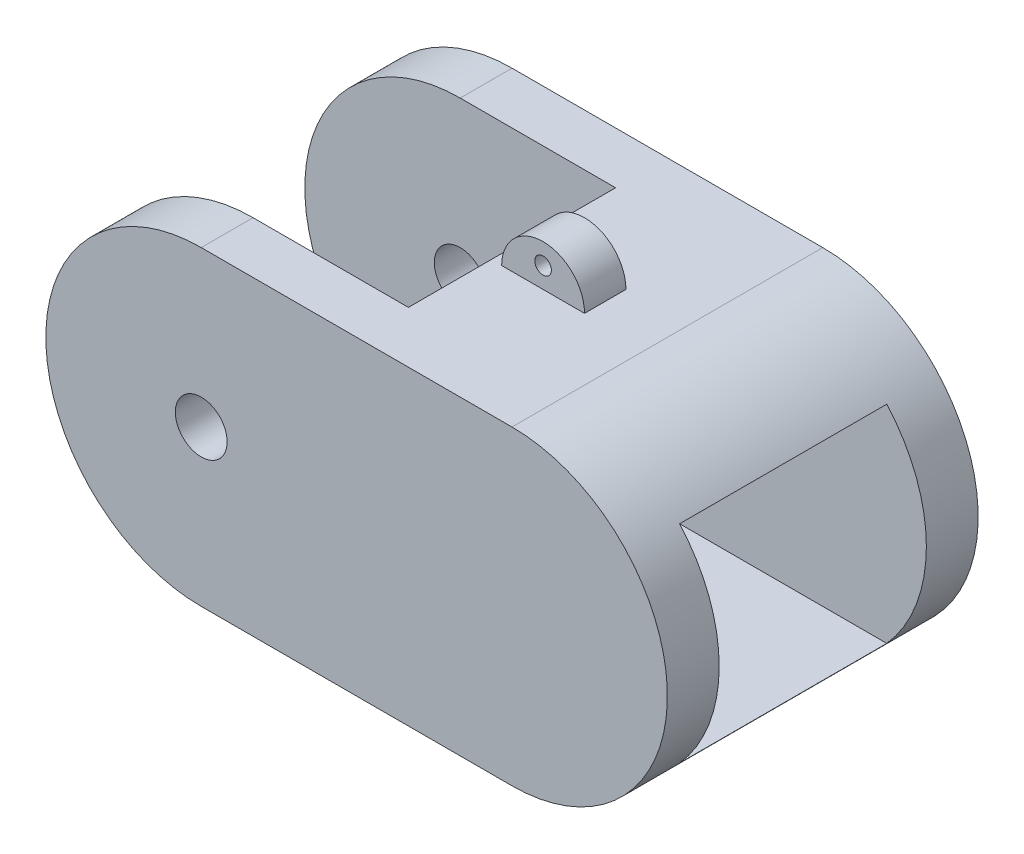
SolidWorks part; units mm, degrees
ref_plane "Front Plane" through (0, 0, 0) normal (0, 0, 1) x (1, 0, 0)
ref_plane "Top Plane" through (0, 0, 0) normal (0, 1, 0) x (1, 0, 0)
ref_plane "Right Plane" through (0, 0, 0) normal (1, 0, 0) x (0, 0, -1)
ref_plane "Right Side Plane" through (0, 0, 9.525) normal (0, 0, 1) x (1, 0, 0)
ref_plane "Inside Plane" through (0, 19.05, 0) normal (0, 1, 0) x (1, 0, 0)
ref_plane "Joint Plane" through (-15.875, 0, 0) normal (1, 0, 0) x (0, 0, -1)
sketch "Sketch1" plane through (0, 0, 0) normal (0, 1, 0) x (1, 0, 0)
  line L1 (-22.225, 9.525) -> (15.875, 9.525)
  line L2 (-22.225, 9.525) -> (-22.225, -9.525)
  line L3 (-22.225, -9.525) -> (15.875, -9.525)
  line L4 (15.875, 9.525) -> (15.875, -9.525)
  dimension "D1" = 38.1
  dimension "D2" = 19.05
  dimension "D3" = 9.525
  dimension "D4" = 15.875
extrude "Boss-Extrude1" add sketch "Sketch1" along normal blind 19.05
sketch "Sketch2" plane through (0, 0, 9.525) normal (0, 0, 1) x (1, 0, 0)
  line L0 (-22.225, 19.05) -> (15.875, 19.05) construction
  line L1 (-22.225, 19.05) -> (-22.225, 0) construction
  line L2 (-22.225, 0) -> (15.875, 0) construction
  line L3 (15.875, 19.05) -> (15.875, 0) construction
  circle A0 centre (-12.7, 9.525) radius 1.5875
  arc A1 (-12.7, 19.05) -> (-12.7, 0) centre (-12.7, 9.525) ccw
  arc A2 (-12.7, 19.05) -> (-12.7, 0) centre (-21.0188, 9.525) ccw
  arc A3 (6.35, 0) -> (6.35, 19.05) centre (6.35, 9.525) ccw
  arc A4 (6.35, 19.05) -> (6.35, 0) centre (13.21, 9.525) cw
extrude "Cut-Extrude2" cut sketch "Sketch2" against normal blind 19.05
sketch "Sketch3" plane through (0, 19.05, 0) normal (0, 1, 0) x (1, 0, 0)
  line L10 (-12.7, 9.525) -> (-12.7, -9.525) construction
  line L11 (-29.3201, 6.35) -> (-12.7, 6.35)
  line L12 (-29.3201, 6.35) -> (-29.3201, -6.35)
  line L13 (-29.3201, -6.35) -> (-12.7, -6.35)
  line L14 (-12.7, 6.35) -> (-12.7, -6.35)
  line L15 (-12.7, 9.525) -> (-22.225, 9.525) construction
  line L16 (-22.225, -9.525) -> (-12.7, -9.525) construction
  dimension "D1" = 3.175
  dimension "D2" = 3.175
extrude "Cut-Extrude3" cut sketch "Sketch3" against normal blind 19.05
sketch "Sketch4" plane through (-15.875, 0, 0) normal (1, 0, 0) x (0, 0, -1)
  line L0 (6.35, 11.1125) -> (6.35, 19.05) construction
  line L1 (6.35, 15.875) -> (-6.35, 15.875)
  line L2 (6.35, 15.875) -> (6.35, 3.175)
  line L3 (6.35, 3.175) -> (-6.35, 3.175)
  line L4 (-6.35, 15.875) -> (-6.35, 3.175)
  line L5 (-6.35, 0) -> (-6.35, 19.05) construction
  line L6 (7.6835, 19.05) -> (-7.6835, 19.05) construction
  line L7 (-6.35, 0) -> (6.35, 0) construction
  dimension "D1" = 3.175
  dimension "D2" = 3.175
extrude "Cut-Extrude4" cut sketch "Sketch4" along normal blind 50.8
sketch "Sketch6" plane through (0, 0, 0) normal (0, 1, 0) x (1, 0, 0)
  line L0 (-12.7, 6.35) -> (-12.7, -6.35) construction
  line L1 (-6.35, -1.905) -> (-1.27, -1.905)
  line L2 (-6.35, -1.905) -> (-6.35, 1.905)
  line L3 (-6.35, 1.905) -> (-1.27, 1.905)
  line L4 (-1.27, -1.905) -> (-1.27, 1.905)
  dimension "D1" = 3.81
  dimension "D2" = 5.08
  dimension "D3" = 6.35
  dimension "D4" = 1.905
extrude "Boss-Extrude2" add sketch "Sketch6" against normal blind 7.62
sketch "Sketch7" plane through (0, 0, 9.525) normal (0, 0, 1) x (1, 0, 0)
  line L4 (-6.35, -2.54) -> (-6.35, 0)
  line L5 (-3.4098, 0) -> (-1.27, 0)
  arc A0 (-1.27, -2.54) -> (-3.81, -5.08) centre (-3.81, -2.54) cw
  arc A1 (-3.81, -5.08) -> (-6.35, -2.54) centre (-3.81, -2.54) cw
  arc A2 (-1.27, -2.54) -> (-2.5465, -1.3339) centre (-2.5113, -2.5752) ccw
  arc A3 (-2.5465, -1.3339) -> (-2.5267, -2.0347) centre (-2.5366, -1.6843) ccw
  arc A4 (-2.5267, -2.0347) -> (-1.895, -2.5752) centre (-2.5328, -2.6811) cw
  arc A5 (-1.895, -2.5752) -> (-3.81, -4.4612) centre (-4.0211, -2.3316) cw
  arc A6 (-3.81, -4.4612) -> (-5.6738, -2.54) centre (-3.5157, -2.311) cw
  arc A7 (-5.6738, -2.54) -> (-3.4098, 0) centre (-1.5579, -3.9296) cw
  arc A8 (-1.27, 0) -> (-6.35, 0) centre (-3.81, -4.4339) cw
extrude "Cut-Extrude6" cut sketch "Sketch7" against normal blind 19.05
sketch "Sketch8" plane through (0, 19.05, 0) normal (0, 1, 0) x (1, 0, 0)
  line L1 (-2.54, 1.27) -> (2.54, 1.27)
  line L2 (-2.54, 1.27) -> (-2.54, -1.27)
  line L3 (-2.54, -1.27) -> (2.54, -1.27)
  line L4 (2.54, 1.27) -> (2.54, -1.27)
  dimension "D1" = 2.54
  dimension "D2" = 5.08
  dimension "D3" = 2.54
  dimension "D4" = 1.27
extrude "Boss-Extrude3" add sketch "Sketch8" along normal blind 2.54
sketch "Sketch9" plane through (0, 0, 9.525) normal (0, 0, 1) x (1, 0, 0)
  line L0 (-2.54, 19.05) -> (2.54, 19.05) construction
  line L1 (2.54, 21.59) -> (2.54, 19.05) construction
  line L2 (-2.54, 21.59) -> (2.54, 21.59) construction
  arc A0 (-2.54, 19.05) -> (2.54, 19.05) centre (0, 19.05) cw
  circle A1 centre (0, 20.32) radius 0.508
  arc A2 (-2.54, 19.05) -> (2.54, 19.05) centre (0, 20.4722) cw
  point P12 (3.81, 20.4722)
  dimension "D1" = 1.27
  dimension "D2" = 2.54
extrude "Cut-Extrude7" cut sketch "Sketch9" against normal blind 19.05
sketch "Sketch10" plane through (0, 19.05, 0) normal (0, 1, 0) x (1, 0, 0)
  line L1 (-12.7, 6.35) -> (-3.175, 6.35)
  line L2 (-12.7, 6.35) -> (-12.7, -6.35)
  line L3 (-12.7, -6.35) -> (-3.175, -6.35)
  line L4 (-3.175, 6.35) -> (-3.175, -6.35)
  point P5 (0, 0)
  dimension "D1" = 9.525
extrude "Cut-Extrude8" cut sketch "Sketch10" against normal blind 3.81
